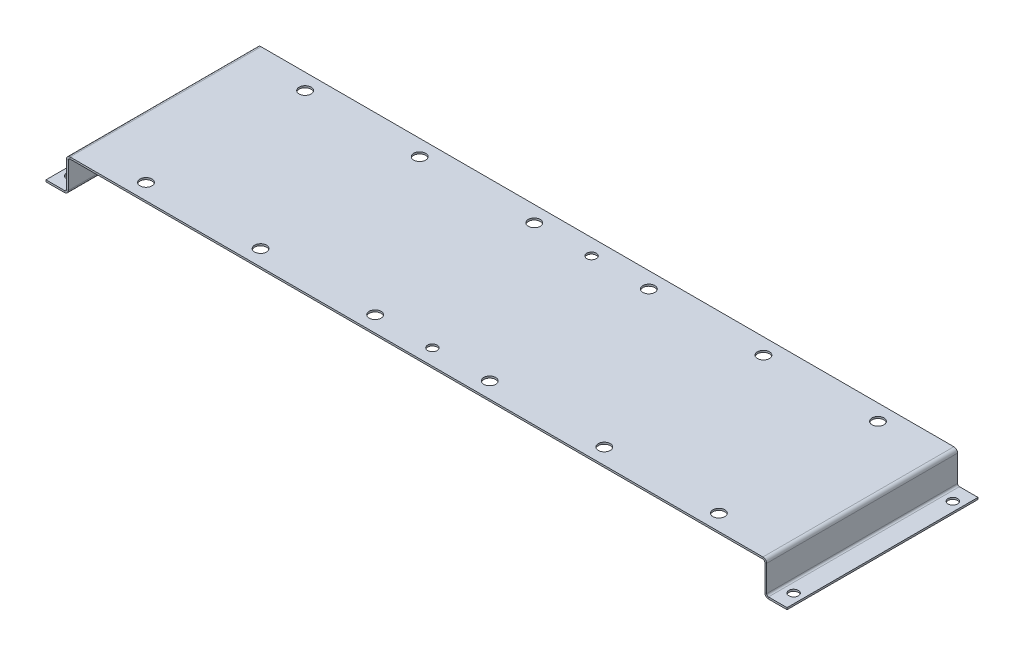
SolidWorks part; units mm, degrees
note: The reader was unsure of these and kept them because the rebuilt part matched: flange length of "Edge-Flange1", "Edge-Flange2".
ref_plane "Front Plane" through (0, 0, 0) normal (0, 0, 1) x (1, 0, 0)
ref_plane "Top Plane" through (0, 0, 0) normal (0, 1, 0) x (1, 0, 0)
ref_plane "Right Plane" through (0, 0, 0) normal (1, 0, 0) x (0, 0, -1)
sketch "Sketch1" plane through (0, 0, 0) normal (0, 1, 0) x (1, 0, 0)
  line L1 (0, 0) -> (279.4, 0)
  line L2 (0, 0) -> (0, 76.2)
  line L3 (0, 76.2) -> (279.4, 76.2)
  line L4 (279.4, 0) -> (279.4, 76.2)
  dimension "D1" = 76.2
  dimension "D2" = 279.4
base flange "Base-Flange1" sketch "Sketch1" thickness 0.7366 reverse thickness direction no parameters "D1"=0.7366
ref_plane "Plane2" through (139.7, 0, 0) normal (-1, 0, 0) x (0, 0, 1)
edge flange "Edge-Flange1" sketch "Sketch8" flange angle 90 flange length 11.2268 flange position material inside bend radius 0.7366 thickness 0.7366 relief rectangular parameters "D6"=10
sketch "Sketch8" plane through (0, -0.7366, 0) normal (-1, 0, 0) x (0, 0, -1)
  line L0 (76.2, 0) -> (0, 0) construction
  line L1 (76.2, 0) -> (0, 0)
  line L2 (0, 0) -> (0, 11.2268)
  line L3 (0, 11.2268) -> (76.2, 11.2268)
  line L4 (76.2, 11.2268) -> (76.2, 0)
  dimension "D1" = 11.2268
bend "EdgeBend1" bend radius 0.7366 bend angle 90 parameters "D5"=1
edge flange "Edge-Flange2" sketch "Sketch11" flange angle 90 flange length 8.89 flange position bend outside bend radius 0.7366 thickness 0.7366 relief rectangular parameters "D6"=10
sketch "Sketch11" plane through (0, -11.9634, 0) normal (0, -1, 0) x (0, 0, 1)
  line L2 (-76.2, 0) -> (-76.2, 8.1534)
  line L3 (-76.2, 8.1534) -> (0, 8.1534)
  line L4 (0, 8.1534) -> (0, 0)
  line L5 (-76.2, 0) -> (0, 0) construction
  line L6 (-76.2, 0) -> (0, 0)
bend "EdgeBend2" bend radius 0.7366 bend angle 90 parameters "D5"=2
hole_wizard "3/32 (0.09375) Diameter Hole1" positions "Sketch22" profile "Sketch21" hole size "3/32" standard "ANSI Inch"
sketch "Sketch22" plane through (0, 0, 0) normal (0, 1, 0) x (1, 0, 0)
  line L1 (0, 76.2) -> (0, 0) construction
  line L2 (279.4, 76.2) -> (1.4732, 76.2) construction
  point P0 (25.4, 69.85)
  dimension "D1" = 25.4
  dimension "D2" = 6.35
sketch "Sketch21" plane through (25.4, 0, -69.85) normal (1, 0, 0) x (0, 0, 1)
  line L0 (0, 0) -> (0, 2.1674)
  line L1 (0, 2.1674) -> (2.3812, 0.7366)
  line L2 (2.3812, 0.7366) -> (2.3812, 0)
  line L5 (2.3812, 0) -> (0, 0)
  line L10 (0, 2.1674) -> (-2.3812, 0.7366) construction
  line L11 (0, -6.35) -> (0, 107.95) construction
  dimension "Hole Dia." = 4.7625
  dimension "Hole Depth" = 0.7366
  dimension "Drill Angle" = 118
hole_wizard "#6 Clearance Hole1" positions "Sketch13" profile "Sketch12" hole size "#6" standard "ANSI Inch" end condition through all
sketch "Sketch13" plane through (0, -12.7, 0) normal (0, 1, 0) x (1, 0, 0)
  line L0 (-4.445, 76.2) -> (-4.445, 0) construction
  line L1 (-8.1534, 76.2) -> (-0.7366, 76.2) construction
  line L2 (-0.7366, 0) -> (-8.1534, 0) construction
  line L4 (-8.1534, 38.1) -> (-0.7366, 38.1) construction
  line L5 (-8.1534, 0) -> (-8.1534, 76.2) construction
  line L6 (-0.7366, 76.2) -> (-0.7366, 0) construction
  point P0 (-4.445, 69.85)
  point P2 (-4.445, 6.35)
  dimension "D1" = 63.5
sketch "Sketch12" plane through (-4.445, -12.7, -69.85) normal (1, 0, 0) x (0, 0, 1)
  line L0 (0, 0) -> (0, 0.7366)
  line L1 (0, 0.7366) -> (1.8986, 0.7366)
  line L2 (1.8986, 0.7366) -> (1.8986, 0)
  line L5 (1.8986, 0) -> (0, 0)
  line L11 (0, -6.35) -> (0, 107.95) construction
  dimension "Thru Hole Dia." = 3.7973
  dimension "Thru Hole Depth" = 0.7366
pattern_linear "LPattern1" count 6 spacing 45.72 along (1, 0, 0) count 2 spacing 63.5 along (0, 0, 1) of "3/32 (0.09375) Diameter Hole1"
mirror "Mirror2" about plane through (139.7, 0, 0) normal (-1, 0, 0) of "Edge-Flange1", "Edge-Flange2", "#6 Clearance Hole1"
bend "MirrorBend3" bend radius 0.7366 bend angle 90 parameters "D5"=3
bend "MirrorBend4" bend radius 0.7366 bend angle 90 parameters "D5"=4
hole_wizard "#6 Clearance Hole2" positions "Sketch24" profile "Sketch23" hole size "#6" standard "ANSI Inch" end condition through all
sketch "Sketch24" plane through (0, 0, 0) normal (0, 1, 0) x (1, 0, 0)
  line L0 (277.9268, 38.1) -> (1.4732, 38.1) construction
  line L1 (277.9268, 0) -> (277.9268, 76.2) construction
  line L2 (1.4732, 76.2) -> (1.4732, 0) construction
  line L3 (139.7, 76.2) -> (139.7, 0) construction
  line L4 (277.9268, 76.2) -> (1.4732, 76.2) construction
  line L5 (1.4732, 0) -> (277.9268, 0) construction
  point P0 (139.7, 69.85)
  point P2 (139.7, 6.35)
  dimension "D1" = 63.5
sketch "Sketch23" plane through (139.7, 0, -69.85) normal (1, 0, 0) x (0, 0, 1)
  line L0 (0, 0) -> (0, 13.4366)
  line L1 (0, 13.4366) -> (1.8986, 13.4366)
  line L2 (1.8986, 13.4366) -> (1.8986, 0)
  line L5 (1.8986, 0) -> (0, 0)
  line L11 (0, -6.35) -> (0, 107.95) construction
  dimension "Thru Hole Dia." = 3.7973
  dimension "Thru Hole Depth" = 13.4366
sketch "Bend-Lines1" plane through (0, 0, 0) normal (0, 1, 0) x (1, 0, 0)
sketch "Bounding-Box1" plane through (0, 0, 0) normal (0, 1, 0) x (1, 0, 0)
sheet metal parameters "Sheet-Metal(1)" thickness 0.7366 parameters "D1"=0.7366
flat pattern "Flat-Pattern(1)" [suppressed]
sketch "Bend-Lines2" plane through (0, 0, 0) normal (0, 1, 0) x (1, 0, 0)
sketch "Bounding-Box2" [suppressed] plane through (0, 0, 0) normal (0, 1, 0) x (1, 0, 0)
sheet metal parameters "Sheet-Metal(2)" thickness 0.7366 parameters "D1"=0.7366
flat pattern "Flat-Pattern(1)" [suppressed]
sketch "Bend-Lines2" plane through (0, 0, 0) normal (0, 1, 0) x (1, 0, 0)
sketch "Bounding-Box2" [suppressed] plane through (0, 0, 0) normal (0, 1, 0) x (1, 0, 0)
bend of the flat pattern "Flatten-<EdgeBend1>1"
sheet metal parameters "Sheet-Metal(3)" thickness 0.7366 parameters "D1"=0.7366
flat pattern "Flat-Pattern(1)" [suppressed]
sketch "Bend-Lines2" plane through (0, 0, 0) normal (0, 1, 0) x (1, 0, 0)
sketch "Bounding-Box2" [suppressed] plane through (0, 0, 0) normal (0, 1, 0) x (1, 0, 0)
bend of the flat pattern "Flatten-<EdgeBend1>1"
bend of the flat pattern "Flatten-<EdgeBend2>1"
sheet metal parameters "Sheet-Metal(4)" thickness 0.7366 parameters "D1"=0.7366
flat pattern "Flat-Pattern(1)" [suppressed]
sketch "Bend-Lines2" plane through (0, 0, 0) normal (0, 1, 0) x (1, 0, 0)
sketch "Bounding-Box2" [suppressed] plane through (0, 0, 0) normal (0, 1, 0) x (1, 0, 0)
bend of the flat pattern "Flatten-<EdgeBend1>1"
bend of the flat pattern "Flatten-<EdgeBend2>1"
sheet metal parameters "Sheet-Metal(11)" thickness 0.7366 parameters "D1"=0.7366
flat pattern "Flat-Pattern(1)" [suppressed]
sketch "Bend-Lines2" plane through (0, 0, 0) normal (0, 1, 0) x (1, 0, 0)
sketch "Bounding-Box2" [suppressed] plane through (0, 0, 0) normal (0, 1, 0) x (1, 0, 0)
bend of the flat pattern "Flatten-<EdgeBend1>1"
bend of the flat pattern "Flatten-<EdgeBend2>1"
sheet metal parameters "Sheet-Metal(12)" thickness 0.7366 parameters "D1"=0.7366
flat pattern "Flat-Pattern(1)" [suppressed]
sketch "Bend-Lines2" plane through (0, 0, 0) normal (0, 1, 0) x (1, 0, 0)
sketch "Bounding-Box2" [suppressed] plane through (0, 0, 0) normal (0, 1, 0) x (1, 0, 0)
bend of the flat pattern "Flatten-<EdgeBend1>1"
bend of the flat pattern "Flatten-<EdgeBend2>1"
sheet metal parameters "Sheet-Metal(14)" thickness 0.7366 parameters "D1"=0.7366
flat pattern "Flat-Pattern(1)" [suppressed]
sketch "Bend-Lines2" plane through (0, 0, 0) normal (0, 1, 0) x (1, 0, 0)
sketch "Bounding-Box2" [suppressed] plane through (0, 0, 0) normal (0, 1, 0) x (1, 0, 0)
bend of the flat pattern "Flatten-<EdgeBend1>1"
bend of the flat pattern "Flatten-<EdgeBend2>1"
bend of the flat pattern "Flatten-<MirrorBend3>1"
bend of the flat pattern "Flatten-<MirrorBend4>1"
sheet metal parameters "Sheet-Metal(15)" thickness 0.7366 parameters "D1"=0.7366
flat pattern "Flat-Pattern(1)" [suppressed]
sketch "Bend-Lines2" plane through (0, 0, 0) normal (0, 1, 0) x (1, 0, 0)
sketch "Bounding-Box2" [suppressed] plane through (0, 0, 0) normal (0, 1, 0) x (1, 0, 0)
bend of the flat pattern "Flatten-<EdgeBend1>1"
bend of the flat pattern "Flatten-<EdgeBend2>1"
bend of the flat pattern "Flatten-<MirrorBend3>1"
bend of the flat pattern "Flatten-<MirrorBend4>1"
